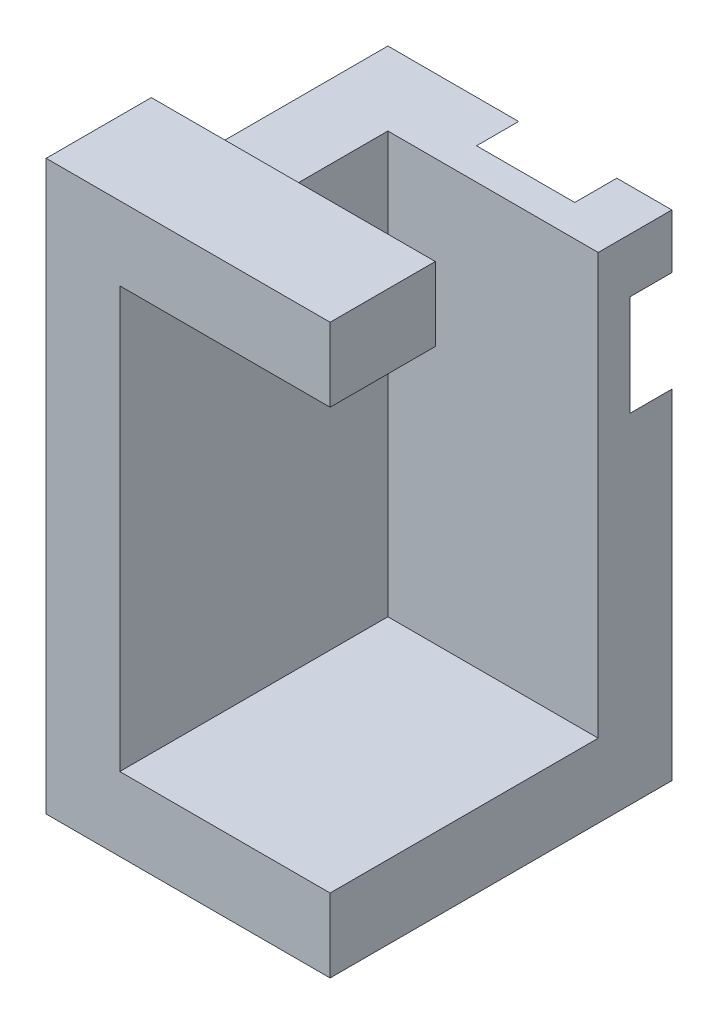
SolidWorks part; units mm, degrees
ref_plane "Front Plane" through (0, 0, 0) normal (0, 0, 1) x (1, 0, 0)
ref_plane "Top Plane" through (0, 0, 0) normal (0, 1, 0) x (1, 0, 0)
ref_plane "Right Plane" through (0, 0, 0) normal (1, 0, 0) x (0, 0, -1)
sketch "Sketch1" plane through (0, 0, 0) normal (0, 0, 1) x (1, 0, 0)
  line L1 (0, 0) -> (27, 0)
  line L2 (0, 0) -> (0, 54)
  line L3 (0, 54) -> (27, 54)
  line L4 (7, 7) -> (7, 47)
  line L5 (27, 54) -> (27, 47)
  line L6 (27, 47) -> (7, 47)
  line L8 (27, 0) -> (27, 7)
  line L9 (27, 7) -> (7, 7)
  dimension "D1" = 40
  dimension "D2" = 7
  dimension "D3" = 20
  dimension "D4" = 7
extrude "Boss-Extrude1" add sketch "Sketch1" along normal blind 10
sketch "Sketch2" plane through (0, 0, 0) normal (0, 0, -1) x (-1, 0, 0)
  line L0 (-7, 47) -> (0, 47)
  line L1 (0, 54) -> (0, 0) construction
  line L2 (0, 47) -> (0, 0)
  line L3 (0, 0) -> (-27, 0)
  line L4 (-27, 0) -> (-27, 7)
  line L5 (-27, 7) -> (-7, 7)
  line L6 (-27, 7) -> (-7, 7) construction
  line L7 (-7, 7) -> (-7, 47) construction
  line L8 (-7, 7) -> (-7, 47)
extrude "Boss-Extrude2" add sketch "Sketch2" along normal blind 15.494
sketch "Sketch3" plane through (0, 0, 0) normal (-1, 0, 0) x (0, 0, 1)
  line L0 (10, 0) -> (-15.494, 0) construction
  line L1 (-15.494, 47) -> (-22.494, 47)
  line L2 (-15.494, 47) -> (-15.494, 0)
  line L3 (-15.494, 0) -> (-22.494, 0)
  line L4 (-22.494, 47) -> (-22.494, 0)
  dimension "D1" = 7
extrude "Boss-Extrude3" add sketch "Sketch3" against normal up to surface (27 mm away) up to face at (27, 3.5, -2.747)
sketch "Sketch5" plane through (0, 0, -22.494) normal (0, 0, -1) x (-1, 0, 0)
  line L0 (-27, 47) -> (0, 47) construction
  line L1 (-27, 0) -> (-27, 47) construction
  circle A1 centre (-17.1, 37.04) radius 11
  dimension "D1" = 22
  dimension "D2" = 9.96
  dimension "D3" = 9.9
extrude "Cut-Extrude2" cut sketch "Sketch5" against normal blind 4
